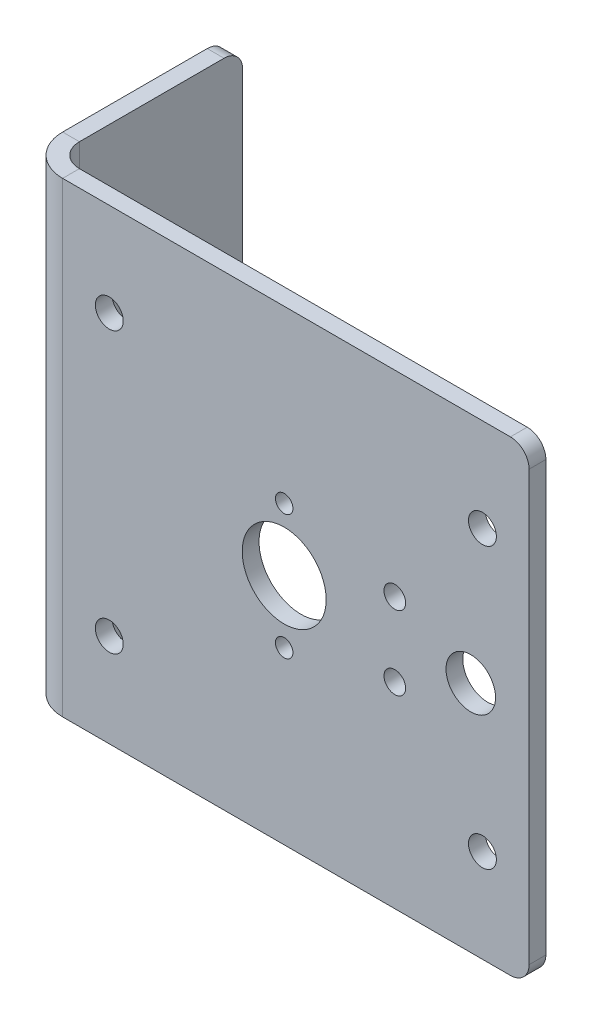
SolidWorks part; units mm, degrees
note: The reader was unsure of these and kept them because the rebuilt part matched: thickness of "Base-Flange1", "Sheet-Metal1", "Sheet-Metal2", "Sheet-Metal3", "Sheet-Metal4", "Sheet-Metal5", "Sheet-Metal7"; bend radius of "Base-Flange1", "BaseBend2".
ref_plane "Front Plane" through (0, 0, 0) normal (1, 0, 0) x (0, 1, 0)
ref_plane "Top Plane" through (0, 0, 0) normal (0, 0, 1) x (0, 1, 0)
ref_plane "Right Plane" through (0, 0, 0) normal (0, 1, 0) x (-1, 0, 0)
sketch "Sketch3" plane through (0, 0, 0) normal (0, 1, 0) x (-1, 0, 0)
  line L0 (-33.3375, 0) -> (33.3375, 0)
  line L2 (33.3375, 0) -> (33.3375, -25.4)
  point P3 (0, 0)
  dimension "D1" = 66.675
  dimension "D3" = 25.4
base flange "Base-Flange1" sketch "Sketch3" end condition mid plane depth 63.5 reverse direction no thickness 2.286 reverse thickness direction yes bend radius 3.175
bend "BaseBend2" bend radius 3.175 bend angle 90 parameters "D5"=1
fillet "Fillet1" radius 2.54 4 edges at (33.3375, -31.75, 1.143) (-34.4805, -31.75, -25.4) (-34.4805, 31.75, -25.4) (33.3375, 31.75, 1.143)
hole_wizard "#25 (0.1495) Diameter Hole1" positions "Sketch8" profile "Sketch9" hole size "#25" standard "ANSI Inch" end condition through all
sketch "Sketch8" plane through (0, 0, 2.286) normal (0, 0, 1) x (1, 0, 0)
  line L0 (1.5875, 0) -> (1.5875, 19.05) construction
  line L1 (1.5875, 19.05) -> (26.9875, 19.05) construction
  line L4 (1.5875, 19.05) -> (-23.8125, 19.05) construction
  line L6 (1.5875, 0) -> (1.5875, -19.05) construction
  line L7 (1.5875, -19.05) -> (-23.8125, -19.05) construction
  line L9 (1.5875, -19.05) -> (26.9875, -19.05) construction
  line L10 (30.7975, 31.75) -> (-30.1625, 31.75) construction
  line L12 (33.3375, 29.21) -> (33.3375, -29.21) construction
  line L13 (30.7975, 31.75) -> (-30.1625, 31.75) construction
  point P0 (-23.8125, 19.05)
  point P2 (26.9875, 19.05)
  point P4 (26.9875, -19.05)
  point P6 (-23.8125, -19.05)
  dimension "D1" = 12.7
  dimension "D2" = 25.4
  dimension "D3" = 31.75
  dimension "D4" = 31.75
sketch "Sketch9" plane through (-23.8125, 19.05, 2.286) normal (1, 0, 0) x (0, -1, 0)
  line L0 (0, 0) -> (0, 27.686)
  line L1 (0, 27.686) -> (1.8986, 27.686)
  line L2 (1.8986, 27.686) -> (1.8986, 0)
  line L5 (1.8986, 0) -> (0, 0)
  line L11 (0, -6.35) -> (0, 107.95) construction
  dimension "Thru Hole Dia." = 3.7973
  dimension "Thru Hole Depth" = 27.686
sketch "Sketch10" plane through (0, 0, 2.286) normal (0, 0, 1) x (1, 0, 0)
  line L0 (33.3375, 0) -> (-33.3375, 0) construction
  line L1 (-22.5183, 0) -> (25.0967, 0) construction
  circle A0 centre (0, 0) radius 5.715
  dimension "D1" = 11.43
extrude "Cut-Extrude1" cut sketch "Sketch10" against normal through all normal cut yes
hole_wizard "17/64 (0.26563) Diameter Hole1" positions "Sketch11" profile "Sketch12" hole size "17/64" standard "ANSI Inch" end condition through all
sketch "Sketch11" plane through (0, 0, 2.286) normal (0, 0, 1) x (1, 0, 0)
  point P0 (25.4, 0)
  dimension "D1" = 25.4
sketch "Sketch12" plane through (25.4, 0, 2.286) normal (1, 0, 0) x (0, -1, 0)
  line L0 (0, 0) -> (0, 27.686)
  line L1 (0, 27.686) -> (3.3735, 27.686)
  line L2 (3.3735, 27.686) -> (3.3735, 0)
  line L5 (3.3735, 0) -> (0, 0)
  line L11 (0, -6.35) -> (0, 107.95) construction
  dimension "Thru Hole Dia." = 6.747
  dimension "Thru Hole Depth" = 27.686
hole_wizard "3/32 (0.09375) Diameter Hole1" positions "Sketch13" profile "Sketch14" hole size "3/32" standard "ANSI Inch" end condition up to next
sketch "Sketch13" plane through (0, 0, 2.286) normal (0, 0, 1) x (1, 0, 0)
  circle A0 centre (0, 0) radius 8.5
  point P0 (0, 8.5)
  point P2 (0, -8.5)
  dimension "D1" = 17
sketch "Sketch14" plane through (0, 8.5, 2.286) normal (1, 0, 0) x (0, -1, 0)
  line L0 (0, 0) -> (0, 2.286)
  line L1 (0, 2.286) -> (1.1906, 2.286)
  line L2 (1.1906, 2.286) -> (1.1906, 0)
  line L5 (1.1906, 0) -> (0, 0)
  line L11 (0, -6.35) -> (0, 107.95) construction
  dimension "Thru Hole Dia." = 2.3812
  dimension "Thru Hole Depth" = 2.286
sketch "Sketch15" plane through (0, 0, 2.286) normal (0, 0, 1) x (1, 0, 0)
  line L0 (0, 0) -> (16.4978, 9.525) construction
  line L1 (16.4978, 9.525) -> (16.4978, -9.525) construction
  line L2 (16.4978, -9.525) -> (0, 0) construction
  circle A0 centre (0, 0) radius 19.05
  point P3 (15.0579, 5.0275)
  point P4 (15.0579, -5.0275)
  dimension "D1" = 38.1
  dimension "D2" = 19.05
  dimension "D3" = 3.175
  dimension "D4" = 3.175
  dimension "D5" = 15.875
  dimension "D6" = 15.875
hole_wizard "#32 (0.116) Diameter Hole1" positions "Sketch18" profile "Sketch19" hole size "#32" standard "ANSI Inch" end condition through all
sketch "Sketch18" plane through (0, 0, 2.286) normal (0, 0, 1) x (1, 0, 0)
  point P0 (15.0579, 5.0275)
  point P3 (15.0579, -5.0275)
sketch "Sketch19" plane through (15.0579, 5.0275, 2.286) normal (1, 0, 0) x (0, -1, 0)
  line L0 (0, 0) -> (0, 27.686)
  line L1 (0, 27.686) -> (1.4732, 27.686)
  line L2 (1.4732, 27.686) -> (1.4732, 0)
  line L5 (1.4732, 0) -> (0, 0)
  line L11 (0, -6.35) -> (0, 107.95) construction
  dimension "Thru Hole Dia." = 2.9464
  dimension "Thru Hole Depth" = 27.686
sketch "Bend-Lines1" [suppressed] plane through (0, 0, 0) normal (0, 1, 0) x (1, 0, 0)
sketch "Bounding-Box1" [suppressed] plane through (0, 0, 0) normal (0, 1, 0) x (1, 0, 0)
sheet metal parameters "Sheet-Metal1" thickness 2.286 parameters "D1"=3.175
flat pattern "Flat-Pattern1" [suppressed]
sketch "Bend-Lines2" plane through (0, 0, 0) normal (0, 1, 0) x (1, 0, 0)
sketch3d "Bounding-Box2" [suppressed]
  line L0 (-63.5, -63.5, 0) -> (0, -63.5, 0) construction
  line L1 (-63.5, 0, 0) -> (0, 0, 0) construction
  line L2 (-63.5, -63.5, 0) -> (-63.5, 0, 0) construction
  line L3 (0, -63.5, 0) -> (0, 0, 0) construction
bend of the flat pattern "Flatten-<BaseBend2>1"
sheet metal parameters "Sheet-Metal2" thickness 2.286 parameters "D1"=3.175, "D7"=1.5875
flat pattern "Flat-Pattern1" [suppressed]
sketch "Bend-Lines2" plane through (0, 0, 0) normal (0, 1, 0) x (1, 0, 0)
sketch3d "Bounding-Box2" [suppressed]
  line L0 (-63.5, -63.5, 0) -> (0, -63.5, 0) construction
  line L1 (-63.5, 0, 0) -> (0, 0, 0) construction
  line L2 (-63.5, -63.5, 0) -> (-63.5, 0, 0) construction
  line L3 (0, -63.5, 0) -> (0, 0, 0) construction
bend of the flat pattern "Flatten-<BaseBend2>2"
sheet metal parameters "Sheet-Metal3" thickness 2.286 parameters "D1"=3.175, "D7"=1.5875
flat pattern "Flat-Pattern1" [suppressed]
sketch "Bend-Lines2" plane through (0, 0, 0) normal (0, 1, 0) x (1, 0, 0)
sketch3d "Bounding-Box2" [suppressed]
  line L0 (-63.5, -63.5, 0) -> (0, -63.5, 0) construction
  line L1 (-63.5, 0, 0) -> (0, 0, 0) construction
  line L2 (-63.5, -63.5, 0) -> (-63.5, 0, 0) construction
  line L3 (0, -63.5, 0) -> (0, 0, 0) construction
bend of the flat pattern "Flatten-<BaseBend2>3"
sheet metal parameters "Sheet-Metal4" thickness 2.286 parameters "D1"=3.175, "D7"=1.5875
flat pattern "Flat-Pattern1" [suppressed]
sketch "Bend-Lines2" plane through (0, 0, 2.286) normal (0, 0, 1) x (1, 0, 0)
  line L0 (33.5538, 31.75) -> (33.5538, -31.75) construction
  line L1 (33.5538, 31.75) -> (33.5538, -31.75) construction
sketch3d "Bounding-Box2" [suppressed]
  line L0 (-66.675, -63.5, 0) -> (13.1327, -63.5, 0) construction
  line L1 (-66.675, 0, 0) -> (13.1327, 0, 0) construction
  line L2 (-66.675, -63.5, 0) -> (-66.675, 0, 0) construction
  line L3 (13.1327, -63.5, 0) -> (13.1327, 0, 0) construction
bend of the flat pattern "Flatten-<BaseBend2>4"
sheet metal parameters "Sheet-Metal5" thickness 2.286 parameters "D1"=3.175, "D7"=1.5875
flat pattern "Flat-Pattern1"
sketch "Bend-Lines2" plane through (0, 0, 2.286) normal (0, 0, 1) x (1, 0, 0)
  line L2 (-33.5538, -31.75) -> (-33.5538, 31.75) construction
  line L3 (-33.5538, -31.75) -> (-33.5538, 31.75) construction
sketch3d "Bounding-Box2" [suppressed]
  line L0 (-92.5077, -63.5, 0) -> (0, -63.5, 0) construction
  line L1 (-92.5077, 0, 0) -> (0, 0, 0) construction
  line L2 (-92.5077, -63.5, 0) -> (-92.5077, 0, 0) construction
  line L3 (0, -63.5, 0) -> (0, 0, 0) construction
bend of the flat pattern "Flatten-<BaseBend2>5"
sheet metal parameters "Sheet-Metal7" thickness 2.286 parameters "D1"=3.175, "D7"=1.5875
flat pattern "Flat-Pattern1"
sketch "Bend-Lines2" plane through (0, 0, 2.286) normal (0, 0, 1) x (1, 0, 0)
  line L2 (-33.5538, -31.75) -> (-33.5538, 31.75) construction
  line L3 (-33.5538, -31.75) -> (-33.5538, 31.75) construction
sketch3d "Bounding-Box2" [suppressed]
  line L0 (-92.5077, -63.5, 0) -> (0, -63.5, 0) construction
  line L1 (-92.5077, 0, 0) -> (0, 0, 0) construction
  line L2 (-92.5077, -63.5, 0) -> (-92.5077, 0, 0) construction
  line L3 (0, -63.5, 0) -> (0, 0, 0) construction
bend of the flat pattern "Flatten-<BaseBend2>5"
